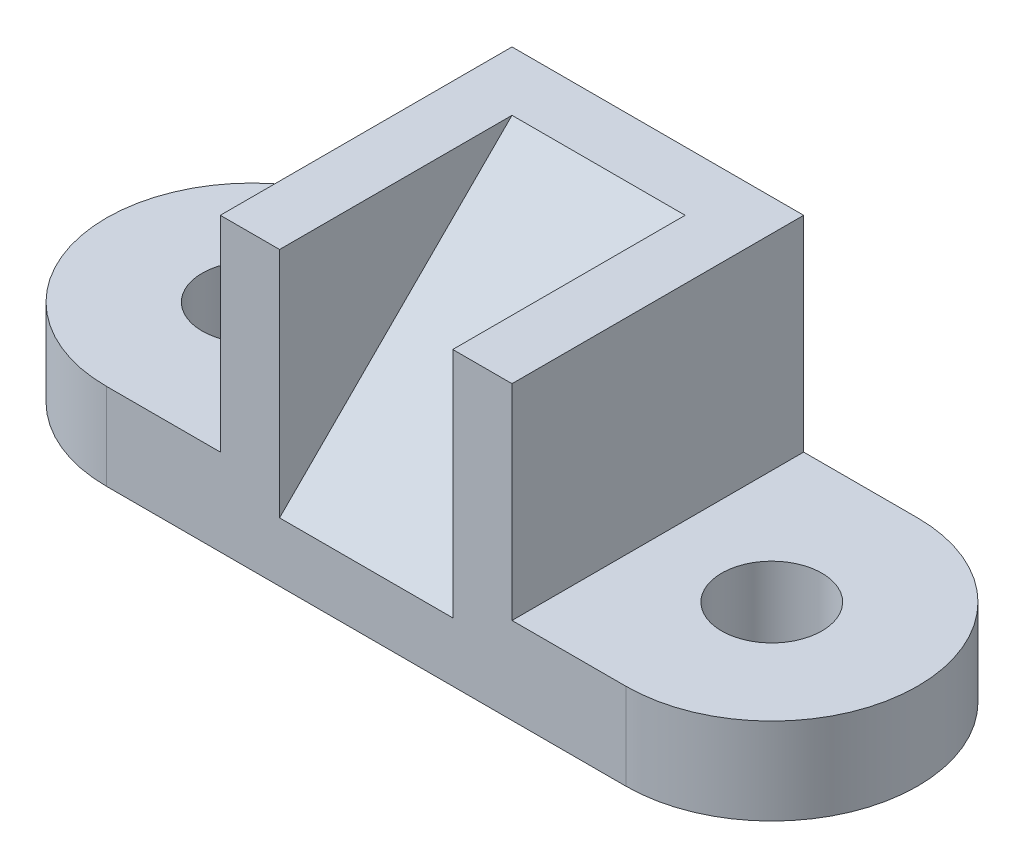
SolidWorks part; units mm, degrees
ref_plane "Front Plane" through (0, 0, 0) normal (0, 0, 1) x (1, 0, 0)
ref_plane "Top Plane" through (0, 0, 0) normal (0, 1, 0) x (1, 0, 0)
ref_plane "Right Plane" through (0, 0, 0) normal (1, 0, 0) x (0, 0, -1)
sketch "Sketch1" plane through (0, 0, 0) normal (0, 1, 0) x (1, 0, 0)
  line L1 (0, 0) -> (114, 0)
  line L3 (0, 64) -> (114, 64)
  arc A0 (114, 0) -> (114, 64) centre (114, 32) ccw
  arc A1 (0, 64) -> (0, 0) centre (0, 32) ccw
  dimension "D1" = 64
  dimension "D2" = 114
extrude "Boss-Extrude1" add sketch "Sketch1" along normal blind 19
sketch "Sketch2" plane through (0, 19, 0) normal (0, 1, 0) x (1, 0, 0)
  line L0 (57, 64) -> (57, 0) construction
  line L1 (114, 64) -> (0, 64) construction
  line L2 (0, 0) -> (114, 0) construction
  line L4 (25, 64) -> (89, 64)
  line L5 (25, 64) -> (25, 0)
  line L6 (25, 0) -> (89, 0)
  line L7 (89, 64) -> (89, 0)
  dimension "D1" = 64
  dimension "D2" = 32
extrude "Boss-Extrude2" add sketch "Sketch2" along normal blind 45
sketch "Sketch3" plane through (0, 19, 0) normal (0, 1, 0) x (1, 0, 0)
  circle A0 centre (0, 32) radius 11
  circle A1 centre (114, 32) radius 11
  arc A2 (114, 0) -> (114, 64) centre (114, 32) ccw construction
  dimension "D1" = 22
  dimension "D2" = 22
  dimension "D3" = 21
extrude "Cut-Extrude1" cut sketch "Sketch3" against normal through all
sketch "Sketch5" plane through (0, 0, 0) normal (0, 0, 1) x (1, 0, 0)
  line L0 (25, 19) -> (89, 19)
shell "Shell3" thickness 13 removed face at (57, 25.5, 0) removed face at (57, 64, -32)
ref_plane "Plane10" through (76, 64, -51) normal (-1, 0, 0) x (0, 0, 1)
sketch "Sketch10" plane through (76, 0, 0) normal (-1, 0, 0) x (0, 0, 1)
  line L0 (-51, 64) -> (-51, 13)
  line L1 (-51, 13) -> (0, 13)
  line L2 (0, 13) -> (-51, 64)
extrude "Boss-Extrude3" add sketch "Sketch10" along normal up to surface (38 mm away) up to face at (38, 38.5, -25.5)
